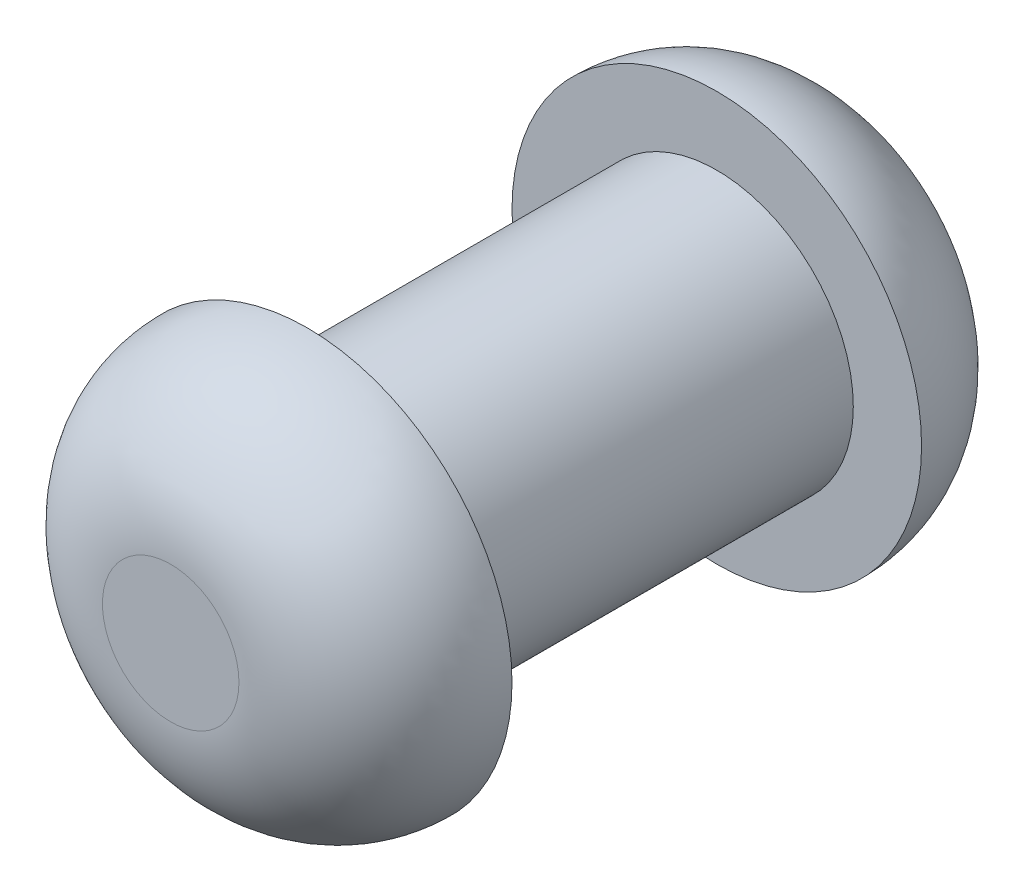
SolidWorks part; units mm, degrees
ref_plane "Ön Düzlem" through (0, 0, 0) normal (0, 0, 1) x (1, 0, 0)
ref_plane "Üst Düzlem" through (0, 0, 0) normal (0, 1, 0) x (1, 0, 0)
ref_plane "Sağ Düzlem" through (0, 0, 0) normal (1, 0, 0) x (0, 0, -1)
sketch "Çizim1" plane through (0, 0, 0) normal (0, 0, 1) x (1, 0, 0)
  circle A0 centre (0, 0) radius 5
extrude "Yükseklik-Ekstrüzyon1" add sketch "Çizim1" along normal blind 15
sketch "Çizim2" plane through (0, 0, 15) normal (0, 0, 1) x (1, 0, 0)
  circle A0 centre (0, 0) radius 7.5
extrude "Yükseklik-Ekstrüzyon2" add sketch "Çizim2" along normal blind 5
fillet "Radyus1" radius 5 1 edges at (7.5, 0, 20)
sketch "Çizim3" plane through (0, 0, 0) normal (0, 0, -1) x (-1, 0, 0)
  circle A0 centre (0, 0) radius 7.5
extrude "Yükseklik-Ekstrüzyon3" add sketch "Çizim3" along normal blind 5
fillet "Radyus2" radius 5 1 edges at (-7.5, 0, -5)
